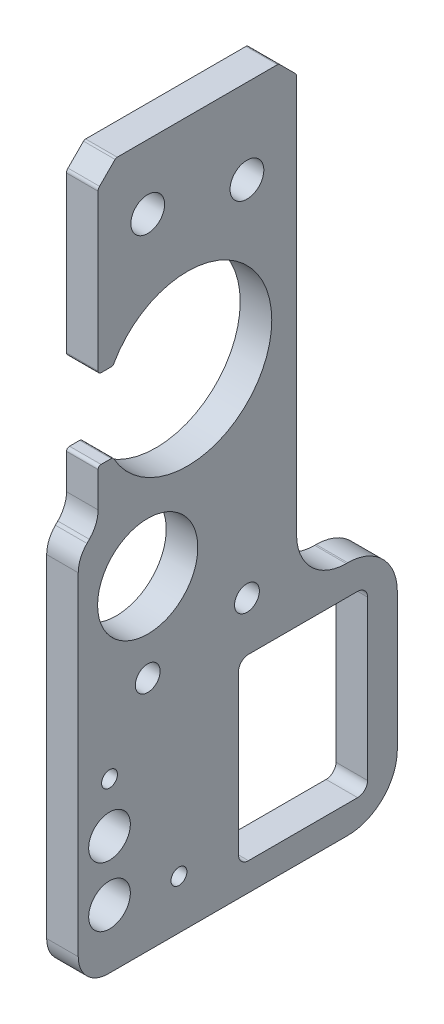
SolidWorks part; units mm, degrees
material "6061 Alloy"
ref_plane "Front Plane" through (0, 0, 0) normal (0, 0, 1) x (1, 0, 0)
ref_plane "Top Plane" through (0, 0, 0) normal (0, 1, 0) x (1, 0, 0)
ref_plane "Right Plane" through (0, 0, 0) normal (1, 0, 0) x (0, 0, -1)
sketch "Sketch1" plane through (0, 0, 0) normal (1, 0, 0) x (0, 0, -1)
  line L2 (0, 0) -> (0, 37.75)
  line L3 (0, 37.75) -> (2, 39.75)
  line L4 (2, 39.75) -> (2, 70.81)
  line L5 (2, 70.81) -> (22, 70.81)
  line L14 (-6.9356, -2) -> (62.4069, -2) construction
  line L15 (7, 37.75) -> (0, 37.75) construction
  line L23 (22, 70.81) -> (22, 23.81)
  line L31 (22, 23.81) -> (32.15, 23.81)
  line L32 (32.15, 23.81) -> (32.15, 0)
  line L33 (32.15, 0) -> (0, 0)
  line L35 (22.65, 20.81) -> (22.65, 2.81) construction
  line L36 (16.15, 20.81) -> (29.15, 20.81)
  line L37 (16.15, 20.81) -> (16.15, 2.81)
  line L38 (16.15, 2.81) -> (29.15, 2.81)
  line L39 (29.15, 20.81) -> (29.15, 2.81)
  circle A0 centre (7, 32.7) radius 5.05
  circle A1 centre (7, 64.31) radius 1.7
  circle A2 centre (17, 62.31) radius 1.7
  circle A5 centre (3.15, 5.95) radius 2.1
  circle A6 centre (3.15, 11.95) radius 2.1
  circle A9 centre (10.15, 4.95) radius 0.8
  circle A10 centre (3.15, 16.95) radius 0.8
  point P1 (7, 23.81)
  point P2 (17, 25.81)
  dimension "D11" = 10.1
  dimension "D13" = 3.4
  dimension "D17" = 15
  dimension "D21" = 2
  dimension "D33" = 4.2
  dimension "D36" = 1.6
  dimension "D4" = 18
  dimension "D5" = 13
  dimension "D22" = 15.75
  dimension "D6" = 16.15
  dimension "D7" = 5
  dimension "D8" = 2
  dimension "D9" = 2
  dimension "D10" = 47
  dimension "D12" = 34.7
  dimension "D14" = 8.5
  dimension "D15" = 6.5
  dimension "D16" = 5
  dimension "D18" = 38.11
  dimension "D19" = 3
  dimension "D20" = 3
  dimension "D23" = 7
  dimension "D24" = 20
  dimension "D25" = 5
  dimension "D28" = 2
  dimension "D30" = 6
  dimension "D32" = 3.15
  dimension "D38" = 12
extrude "Boss-Extrude1" add sketch "Sketch1" along normal blind 3.18
sketch "Sketch3" plane through (0, 0, 0) normal (1, 0, 0) x (0, 0, -1)
  line L4 (2, 70.81) -> (2, 39.75) construction
  circle A0 centre (-7, 41.6196) radius 5.5
  circle A6 centre (7, 32.7) radius 5.05 construction
  dimension "D1" = 11
  dimension "D3" = 16.6
  dimension "D2" = 9
extrude "Cut-Extrude4" [suppressed] cut sketch "Sketch3" against normal through all
sketch "Sketch8" plane through (3.18, 0, 0) normal (1, 0, 0) x (0, 0, -1)
  line L0 (2, 70.81) -> (2, 39.75) construction
  line L1 (11, 48.8109) -> (2, 48.8109) construction
  line L2 (2, 52.8109) -> (3.5, 52.8109)
  line L3 (3.5, 44.8109) -> (2, 44.8109)
  line L4 (2, 44.8109) -> (2, 52.8109)
  arc A0 (3.5, 44.8109) -> (3.5, 52.8109) centre (11, 48.8109) ccw
  circle A1 centre (7, 32.7) radius 5.05 construction
  point P11 (2, 48.8109)
  dimension "D1" = 16.6
  dimension "D2" = 17
  dimension "D3" = 9
  dimension "D4" = 8
extrude "Cut-Extrude5" cut sketch "Sketch8" against normal through all
fillet "Fillet2" radius 3 3 edges at (1.59, 37.75, 0) (1.59, 39.75, -2) (1.59, 0, 0)
fillet "Chamfer2" radius 1.8 2 edges at (1.59, 70.81, -22) (1.59, 70.81, -2) profile chamfer
fillet "Fillet4" radius 0.5 2 edges at (1.59, 69.01, -2) (1.59, 69.01, -22)
fillet "Fillet5" radius 0.3 6 edges at (1.59, 70.81, -20.2) (1.59, 70.81, -3.8) (1.59, 52.8109, -2) (1.59, 52.8109, -3.5) (1.59, 44.8109, -3.5) (1.59, 44.8109, -2)
sketch "BallRef" [suppressed] plane through (0, 0, 0) normal (-1, 0, 0) x (0, 0, 1)
  line L0 (-31.524, -10.56) -> (65.6624, -10.56) construction
  line L1 (-0.75, 32.7) -> (-0.75, 29.3885) construction
  line L2 (-0.75, 29.3885) -> (31.3703, 29.3885) construction
  line L3 (31.3703, 10.85) -> (31.3703, 29.3885) construction
  line L4 (1.092, -10.56) -> (-13.908, 4.44) construction
  line L5 (-13.908, 4.44) -> (-13.908, -10.56) construction
  line L6 (-13.908, -10.56) -> (1.092, -10.56) construction
  circle A0 centre (-7, 32.7) radius 6.25 construction
  circle A1 centre (9.9603, 10.85) radius 21.41 construction
  dimension "D1" = 12.5
  dimension "D2" = 42.82
  dimension "D3" = 43.26
  dimension "D4" = 45
  dimension "D5" = 15
hole_wizard "M2x0.4 Tapped Hole1" positions "3DSketch1" profile "Sketch12" tap size "M2x0.4" standard "ANSI Metric" end condition through all
sketch3d "3DSketch1"
  line L0 (3.18, 16.95, -3.15) -> (0, 16.95, -3.15) construction
  line L1 (3.18, 4.95, -10.15) -> (0, 4.95, -10.15) construction
  point P0 (0, 16.95, -3.15)
  point P4 (0, 4.95, -10.15)
sketch "Sketch12" plane through (0, 16.95, -3.15) normal (0, 1, 0) x (0, 0, 1)
  line L0 (0, 0) -> (0, 3.18)
  line L1 (0, 3.18) -> (0.8, 3.18)
  line L2 (0.8, 3.18) -> (0.8, 0)
  line L5 (0.8, 0) -> (0, 0)
  line L11 (0, -6.35) -> (0, 107.95) construction
  dimension "Thru Tap Drill Dia." = 1.6
  dimension "Thru Tap Drill Depth" = 3.18
cosmetic thread "Hole Thread3" parameters "D2"=2
cosmetic thread "Hole Thread4" parameters "D2"=2
fillet "Fillet9" radius 1 4 edges at (1.59, 2.81, -29.15) (1.59, 2.81, -16.15) (1.59, 20.81, -29.15) (1.59, 20.81, -16.15)
fillet "Fillet11" radius 5 3 edges at (1.59, 0, -32.15) (1.59, 23.81, -22) (1.59, 23.81, -32.15)
hole_wizard "M3x0.5 Tapped Hole1" positions "Sketch13" profile "Sketch14" tap size "M3x0.5" standard "ANSI Metric" end condition through all
sketch "Sketch13" plane through (3.18, 0, 0) normal (1, 0, 0) x (0, 0, -1)
  point P0 (7, 23.81)
  point P3 (17, 25.81)
sketch "Sketch14" plane through (3.18, 23.81, -7) normal (0, 1, 0) x (0, 0, -1)
  line L0 (0, 0) -> (0, 3.18)
  line L1 (0, 3.18) -> (1.25, 3.18)
  line L2 (1.25, 3.18) -> (1.25, 0)
  line L5 (1.25, 0) -> (0, 0)
  line L11 (0, -6.35) -> (0, 107.95) construction
  dimension "Thru Tap Drill Dia." = 2.5
  dimension "Thru Tap Drill Depth" = 3.18
cosmetic thread "Hole Thread5" [suppressed] parameters "D2"=3
cosmetic thread "Hole Thread6" [suppressed] parameters "D2"=3
equation "\"7.5.00mm\"=5"
